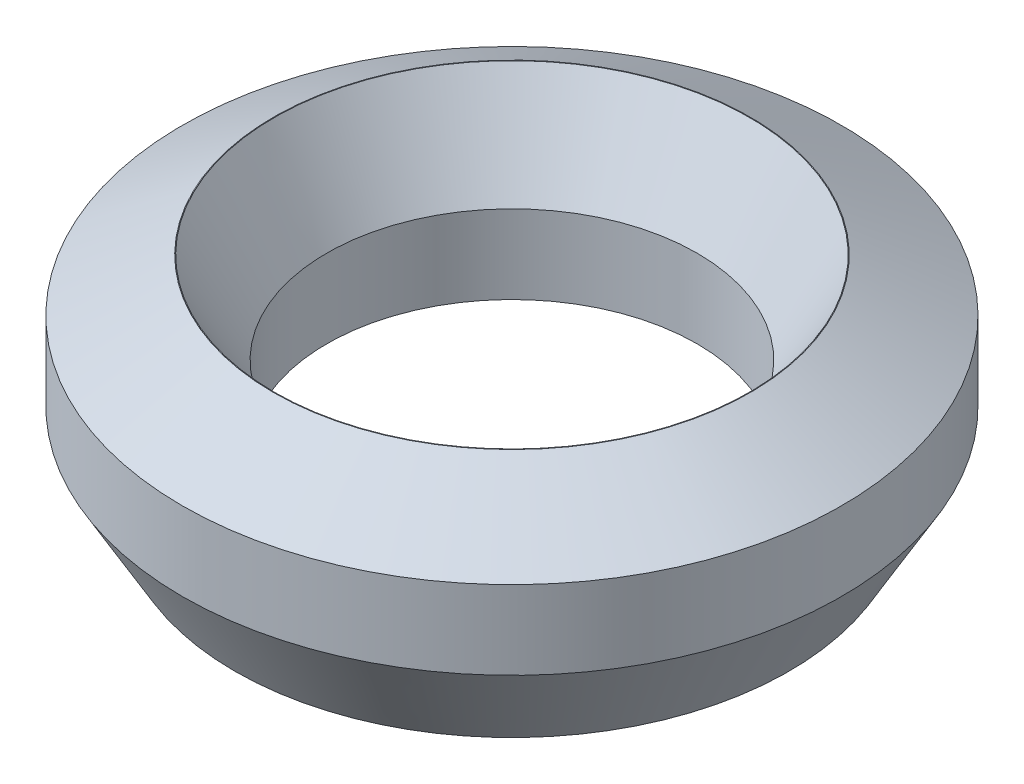
SolidWorks part; units mm, degrees
ref_plane "Front Plane" through (0, 0, 0) normal (0, 0, 1) x (1, 0, 0)
ref_plane "Top Plane" through (0, 0, 0) normal (0, 1, 0) x (1, 0, 0)
ref_plane "Right Plane" through (0, 0, 0) normal (1, 0, 0) x (0, 0, -1)
sketch "Sketch1" plane through (0, 0, 0) normal (0, 1, 0) x (1, 0, 0)
  circle A0 centre (0, 0) radius 17.5
  dimension "SLEEVE_OD" = 35
extrude "Boss-Extrude1" add sketch "Sketch1" along normal blind 11.801
sketch "Sketch2" plane through (0, 0, 0) normal (0, 1, 0) x (1, 0, 0)
  circle A0 centre (0, 0) radius 9.8329
  dimension "BORE_D" = 19.6659
extrude "Cut-Extrude1" cut sketch "Sketch2" along normal through all
chamfer "Chamfer1" distance 2.7928 angle 60 4 edges at (0, 11.801, 9.8329) (0, 0, 9.8329) (0, 0, 17.5) (0, 11.801, 17.5) first distance on face at (0, 11.801, 9.8329) first distance on face at (0, 0, 9.8329) first distance on face at (0, 11.801, 17.5)
